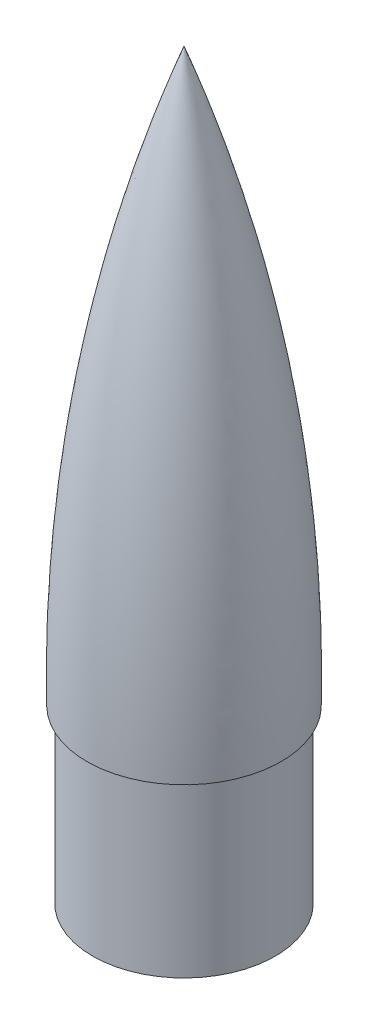
SolidWorks part; units mm, degrees
ref_plane "Спереди" through (0, 0, 0) normal (0, 0, 1) x (1, 0, 0)
ref_plane "Сверху" through (0, 0, 0) normal (0, 1, 0) x (1, 0, 0)
ref_plane "Справа" through (0, 0, 0) normal (1, 0, 0) x (0, 0, -1)
sketch "Эскиз1" plane through (0, 0, 0) normal (0, 1, 0) x (1, 0, 0)
  circle A0 centre (0, 0) radius 15
  circle A1 centre (0, 0) radius 16
  dimension "D1" = 32
  dimension "D2" = 30
extrude "Бобышка-Вытянуть1" add sketch "Эскиз1" along normal blind 30
sketch "Эскиз5" plane through (0, 0, 0) normal (0, 0, 1) x (1, 0, 0)
  line L0 (0, 100) -> (0, 0) construction
  line L1 (0, 30) -> (0, 130)
  line L2 (0, 30) -> (-17, 30)
  line L3 (16, 30) -> (-16, 30) construction
  arc A1 (0, 130) -> (-17, 30) centre (257.5302, 34.7749) ccw
revolve "Повернуть1" add sketch "Эскиз5" angle 360 about L0
sketch "Эскиз6" plane through (0, 0, 0) normal (0, 0, 1) x (1, 0, 0)
  line L2 (0, 128) -> (-1.2853, 123.6776) construction
  line L3 (-1.2853, 123.6776) -> (-2.1438, 120.7719) construction
  line L9 (-2.1438, 120.7719) -> (-6.1212, 103.936) construction
  line L20 (0, 30) -> (0, 130) construction
  line L21 (0, 128) -> (0, 30)
  line L22 (-2, 32) -> (-2, 118.078)
  line L23 (-15.0274, 32) -> (-2, 32)
  line L26 (0, 30) -> (-15, 30)
  line L27 (0, 30) -> (-17, 30) construction
  line L28 (-15.0312, 37.1518) -> (-15.1484, 32.1802) construction
  line L29 (-15.1484, 32.1802) -> (-15, 30) construction
  arc A5 (-2, 118.078) -> (-15.0274, 32) centre (257.5302, 34.7749) ccw
  arc A6 (-6.1212, 103.936) -> (-15.0312, 37.1518) centre (257.5302, 34.7749) ccw
  spline S0 degree 2 poles (-15.0312, 37.1518) (-15.1484, 32.1802) (-15, 30) knots 0 0 0 1 1 1
  spline S1 degree 3 poles (0, 128) (-1.2853, 123.6776) (-2.1438, 120.7719) (-6.1212, 103.936) knots 0 0 0 0 1 1 1 1
  point P0 (0, 128)
  dimension "D2" = 2
  dimension "D3" = 2
  dimension "D1" = 2
revolve "Вырез-Повернуть1" cut sketch "Эскиз6" angle 360 about L21
